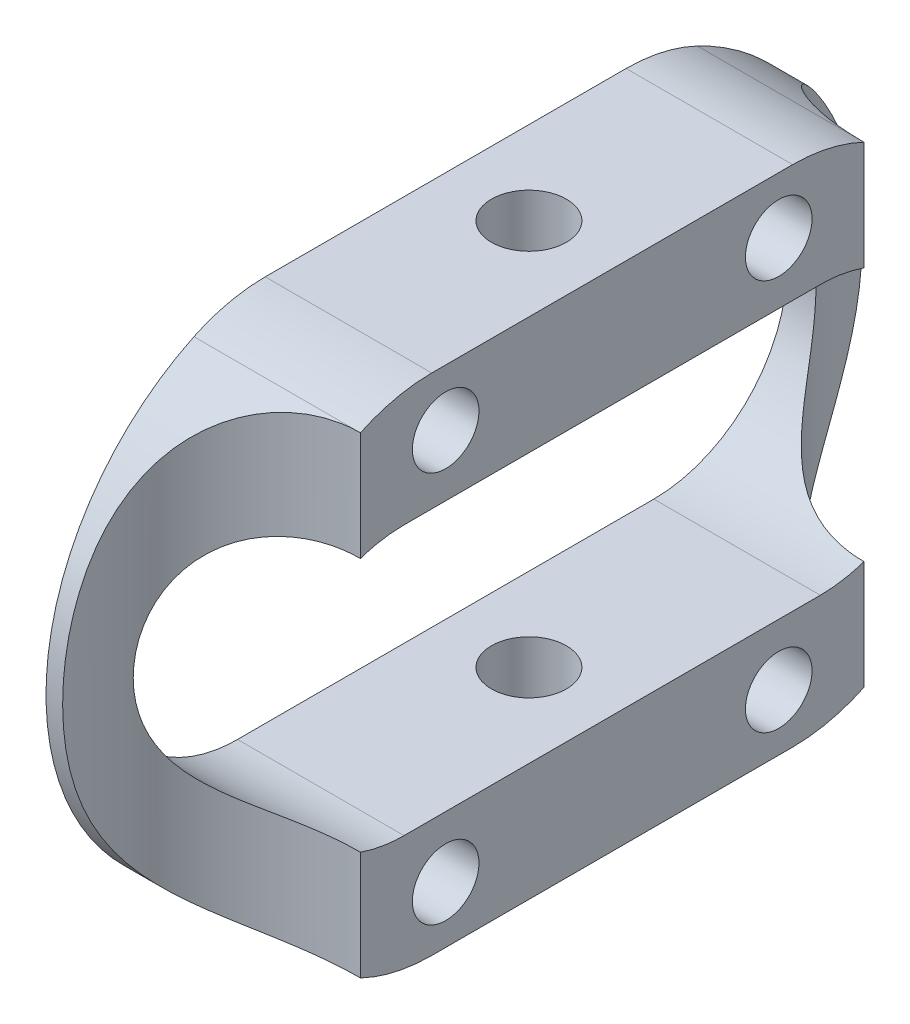
SolidWorks part; units mm, degrees
ref_plane "Płaszczyzna przednia" through (0, 0, 0) normal (0, 0, 1) x (1, 0, 0)
ref_plane "Płaszczyzna górna" through (0, 0, 0) normal (0, 1, 0) x (1, 0, 0)
ref_plane "Płaszczyzna prawa" through (0, 0, 0) normal (1, 0, 0) x (0, 0, -1)
sketch "Szkic1" plane through (0, 0, 0) normal (1, 0, 0) x (0, 0, -1)
  line L0 (25, -16.1572) -> (-25, -16.1572)
  line L1 (0, 16.1572) -> (0, -16.1572) construction
  line L2 (-41, 0) -> (41, 0) construction
  line L3 (25, 16.1572) -> (-25, 16.1572)
  line L4 (-25, -16.1572) -> (25, -16.1572)
  line L5 (-21.6718, -30.2948) -> (21.6718, -30.2948)
  line L6 (21.6718, 30.2948) -> (-21.6718, 30.2948)
  circle A0 centre (-20, 23.5) radius 4
  circle A1 centre (20, 23.5) radius 4
  circle A2 centre (-20, -23.5) radius 4
  circle A3 centre (20, -23.5) radius 4
  ellipse E0 centre (-25, 0) end of major axis (-25, 16.1572) minor radius 16 (-25, 16.1572) -> (-25, -16.1572) ccw
  ellipse E1 centre (25, 0) end of major axis (25, 16.1572) minor radius 16 (25, -16.1572) -> (25, 16.1572) ccw
  ellipse E2 centre (-21.6718, -10.0983) end of major axis (-21.6718, 10.0983) minor radius 20 (-30.2337, -28.3506) -> (-21.6718, -30.2948) ccw
  ellipse E3 centre (21.6718, -10.0983) end of major axis (21.6718, -30.2948) minor radius 20 (21.6718, -30.2948) -> (30.2337, -28.3506) ccw
  ellipse E4 centre (16.9348, 0) end of major axis (16.9348, -31.3705) minor radius 31.0652 (30.2337, -28.3506) -> (30.2337, 28.3506) ccw
  ellipse E5 centre (21.6718, 10.0983) end of major axis (21.6718, -10.0983) minor radius 20 (30.2337, 28.3506) -> (21.6718, 30.2948) ccw
  ellipse E6 centre (-21.6718, 10.0983) end of major axis (-21.6718, -10.0983) minor radius 20 (-21.6718, 30.2948) -> (-30.2337, 28.3506) ccw
  ellipse E7 centre (-16.9348, 0) end of major axis (-16.9348, -31.3705) minor radius 31.0652 (-30.2337, 28.3506) -> (-30.2337, -28.3506) ccw
  point P0 (-20, 23.5)
  point P2 (20, 23.5)
  point P3 (20, -23.5)
  point P11 (-20, -23.5)
  dimension "D1" = 23.5
  dimension "D2" = 20
  dimension "D3" = 1.6718
  dimension "D4" = 9
  dimension "D5" = 14.1304
  dimension "D6" = 16.9348
  dimension "D7" = 20
  dimension "D8" = 21.6718
  dimension "D9" = 25
  dimension "D10" = 9
  dimension "D18" = 23.5
extrude "Dodanie-wyciągnięcie1" add sketch "Szkic1" along normal blind 20 contours E6 E7 E2 L5 E3 E4 E5 L6 A0 A1 A2 A3 E1 L0 E0 L3 region at (0, -28.6953, 25.8101)
sketch "Szkic2" plane through (0, -30.2948, 0) normal (0, -1, 0) x (1, 0, 0)
  line L1 (0, 0) -> (20, 0) construction
  line L2 (20, 21.6718) -> (20, -21.6718) construction
  line L8 (20, 48) -> (0, 48) construction
  line L11 (2, 48) -> (2, 49.8717)
  line L12 (2, 49.8717) -> (22.128, 49.8717)
  line L13 (22.128, 49.8717) -> (22.128, 30.2337)
  line L14 (22.128, 30.2337) -> (20, 30.2337)
  line L15 (22.128, -30.2337) -> (20, -30.2337)
  line L16 (22.128, -49.8717) -> (22.128, -30.2337)
  line L17 (2, -49.8717) -> (22.128, -49.8717)
  line L18 (2, -48) -> (2, -49.8717)
  arc A2 (20, 30.2337) -> (2, 48) centre (19.8831, 48.1169) cw
  arc A4 (20, -30.2337) -> (2, -48) centre (19.8831, -48.1169) ccw
extrude "Wytnij-wyciągnięcie4" cut sketch "Szkic2" against normal through all both and the other way through all
hole_wizard "Pogłębienie stożkowe pod M8 Śrubę z łbem soczewkowym1" positions "Szkic 3D1" profile "Szkic4" countersink size "M8" standard "ISO" end condition through all
sketch3d "Szkic 3D1"
  line L0 (0, -30.2948, 21.6718) -> (0, -30.2948, -21.6718) construction
  line L1 (0, 0, 0) -> (20.0884, 0, 0) construction
  point P0 (10, -30.2948, 0)
  dimension "D1" = 10
sketch "Szkic4" plane through (10, -30.2948, 0) normal (1, 0, 0) x (0, 0, -1)
  line L0 (0, 0) -> (0, 60.5897)
  line L1 (0, 60.5897) -> (4.5, 60.5897)
  line L2 (4.5, 60.5897) -> (4.5, 4.15)
  line L3 (4.5, 4.15) -> (8.65, 0)
  line L5 (8.65, 0) -> (0, 0)
  line L6 (-4.5, 4.15) -> (-8.65, 0) construction
  line L11 (0, -6.35) -> (0, 107.95) construction
  dimension "Średnica otworu na wylot" = 9
  dimension "Głębokość otworu na wylot" = 60.5897
  dimension "Średnica zewnętrznego pogłębienia stożkowego" = 17.3
  dimension "Kąt zewnętrznego pogłębienia stożkowego" = 90
